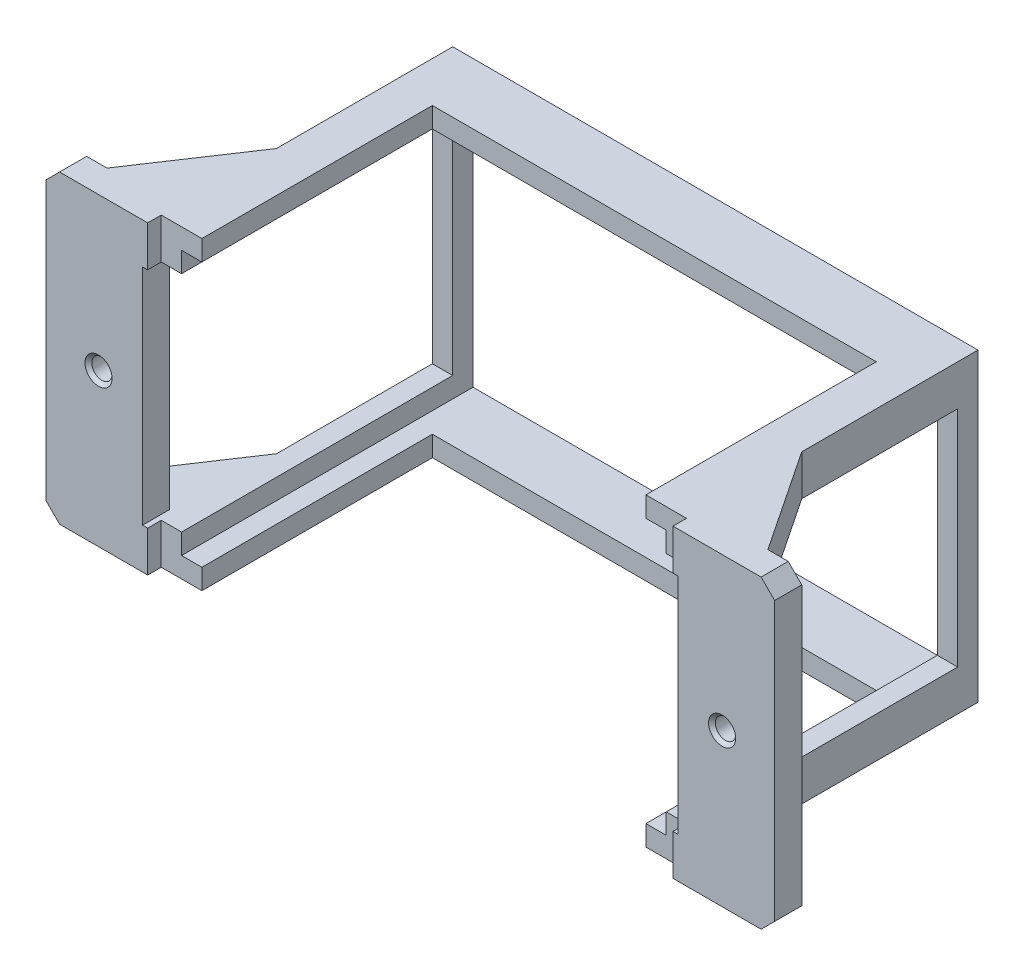
SolidWorks part; units mm, degrees
ref_plane "前视基准面" through (0, 0, 0) normal (0, 0, 1) x (1, 0, 0)
ref_plane "上视基准面" through (0, 0, 0) normal (0, 1, 0) x (1, 0, 0)
ref_plane "右视基准面" through (0, 0, 0) normal (1, 0, 0) x (0, 0, -1)
sketch "草图1" plane through (0, 0, 0) normal (0, 0, 1) x (1, 0, 0)
  line L0 (-38.75, 22.5) -> (38.75, 22.5)
  line L1 (-35.75, 19.5) -> (35.75, 19.5)
  line L2 (-35.75, 19.5) -> (-35.75, -19.5)
  line L3 (-35.75, -19.5) -> (35.75, -19.5)
  line L4 (35.75, 19.5) -> (35.75, -19.5)
  line L5 (38.75, 22.5) -> (38.75, -22.5)
  line L6 (-38.75, -22.5) -> (38.75, -22.5)
  line L7 (-38.75, 22.5) -> (-38.75, -22.5)
  dimension "D1" = 71.5
  dimension "D2" = 35.75
  dimension "D3" = 39
  dimension "D4" = 19.5
  dimension "D5" = 3
extrude "凸台-拉伸1" add sketch "草图1" along normal blind 3
sketch "草图2" plane through (0, 0, 3) normal (0, 0, 1) x (1, 0, 0)
  line L0 (0, 0) -> (0, 50000) construction
  line L1 (38.75, 22.5) -> (35.75, 22.5)
  line L2 (38.75, 22.5) -> (38.75, 19.5)
  line L3 (38.75, 19.5) -> (35.75, 19.5)
  line L4 (35.75, 22.5) -> (35.75, 19.5)
  line L5 (0, 0) -> (50000, 0) construction
  line L6 (-35.75, 22.5) -> (-35.75, 19.5)
  line L7 (-38.75, 19.5) -> (-35.75, 19.5)
  line L8 (-38.75, 22.5) -> (-38.75, 19.5)
  line L9 (-38.75, 22.5) -> (-35.75, 22.5)
  line L10 (-38.75, -22.5) -> (-35.75, -22.5)
  line L11 (-38.75, -22.5) -> (-38.75, -19.5)
  line L12 (-38.75, -19.5) -> (-35.75, -19.5)
  line L13 (-35.75, -22.5) -> (-35.75, -19.5)
  line L14 (35.75, -22.5) -> (35.75, -19.5)
  line L15 (38.75, -19.5) -> (35.75, -19.5)
  line L16 (38.75, -22.5) -> (38.75, -19.5)
  line L17 (38.75, -22.5) -> (35.75, -22.5)
extrude "凸台-拉伸2" add sketch "草图2" along normal blind 40
sketch "草图3" plane through (0, 0, 3) normal (0, 0, 1) x (1, 0, 0)
  line L0 (38.75, -19.5) -> (38.75, 19.5) construction
  line L1 (35.75, 19.5) -> (38.75, 19.5)
  line L2 (35.75, 19.5) -> (35.75, 16.5)
  line L3 (35.75, 16.5) -> (38.75, 16.5)
  line L4 (38.75, 19.5) -> (38.75, 16.5)
  line L5 (35.75, 22.5) -> (-35.75, 22.5) construction
  line L6 (35.75, 19.5) -> (32.75, 19.5)
  line L7 (35.75, 19.5) -> (35.75, 22.5)
  line L8 (35.75, 22.5) -> (32.75, 22.5)
  line L9 (32.75, 19.5) -> (32.75, 22.5)
  line L10 (0, 0) -> (0, 50000) construction
  line L11 (0, 0) -> (50000, 0) construction
  line L12 (-32.75, 19.5) -> (-32.75, 22.5)
  line L13 (-35.75, 22.5) -> (-32.75, 22.5)
  line L14 (-35.75, 19.5) -> (-35.75, 22.5)
  line L15 (-35.75, 19.5) -> (-32.75, 19.5)
  line L16 (-38.75, 19.5) -> (-38.75, 16.5)
  line L17 (-35.75, 16.5) -> (-38.75, 16.5)
  line L18 (-35.75, 19.5) -> (-35.75, 16.5)
  line L19 (-35.75, 19.5) -> (-38.75, 19.5)
  line L20 (-35.75, -19.5) -> (-38.75, -19.5)
  line L21 (-35.75, -19.5) -> (-35.75, -16.5)
  line L22 (-35.75, -16.5) -> (-38.75, -16.5)
  line L23 (-38.75, -19.5) -> (-38.75, -16.5)
  line L24 (-35.75, -19.5) -> (-32.75, -19.5)
  line L25 (-35.75, -19.5) -> (-35.75, -22.5)
  line L26 (-35.75, -22.5) -> (-32.75, -22.5)
  line L27 (-32.75, -19.5) -> (-32.75, -22.5)
  line L28 (32.75, -19.5) -> (32.75, -22.5)
  line L29 (35.75, -22.5) -> (32.75, -22.5)
  line L30 (35.75, -19.5) -> (35.75, -22.5)
  line L31 (35.75, -19.5) -> (32.75, -19.5)
  line L32 (38.75, -19.5) -> (38.75, -16.5)
  line L33 (35.75, -16.5) -> (38.75, -16.5)
  line L34 (35.75, -19.5) -> (35.75, -16.5)
  line L35 (35.75, -19.5) -> (38.75, -19.5)
  line M5 (35.75, 19.5) -> (35.75, -19.5)
  line M6 (35.75, -19.5) -> (38.75, -19.5)
  line M7 (38.75, -19.5) -> (38.75, 19.5)
  line M8 (38.75, 19.5) -> (35.75, 19.5)
  dimension "D1" = 3
  dimension "D2" = 3
extrude "凸台-拉伸3" add sketch "草图3" along normal blind 40 contours L23 L20 L21 L22 | L27 L24 L25 L26 | L30 L31 L28 L29 | L33 M5 M6 M7 | L3 M5 M7 M8 | L9 L6 L7 L8 | L14 L15 L12 L13 | L18 L19 L16 L17 region at (34.25, -21, 3) region at (37.25, 18, 3) region at (34.25, 21, 3) region at (37.25, -18, 3) region at (-34.25, 21, 3) region at (-37.25, 18, 3) region at (-37.25, -18, 3) region at (-34.25, -21, 3)
sketch "草图4" plane through (0, 0, 43) normal (0, 0, 1) x (1, 0, 0)
  line L0 (38.75, -22.5) -> (38.75, -16.5) construction
  line L1 (38.75, 22.5) -> (53.75, 22.5)
  line L2 (38.75, 22.5) -> (38.75, 16.5)
  line L3 (38.75, 16.5) -> (39.5, 16.5)
  line L6 (39.5, 16.5) -> (39.5, -16.5)
  line L9 (39.5, -16.5) -> (38.75, -16.5)
  line L10 (53.75, 22.5) -> (53.75, -22.5)
  line L11 (53.75, -22.5) -> (38.75, -22.5)
  line L12 (38.75, -16.5) -> (38.75, -22.5)
  line L13 (32.75, -22.5) -> (38.75, -22.5) construction
  line L14 (35.75, -16.5) -> (38.75, -16.5) construction
  line L15 (35.75, 16.5) -> (38.75, 16.5) construction
  line L16 (0, 0) -> (0, 50000) construction
  line L17 (-38.75, -16.5) -> (-38.75, -22.5)
  line L18 (-53.75, -22.5) -> (-38.75, -22.5)
  line L19 (-53.75, 22.5) -> (-53.75, -22.5)
  line L20 (-39.5, -16.5) -> (-38.75, -16.5)
  line L21 (-39.5, 16.5) -> (-39.5, -16.5)
  line L22 (-38.75, 16.5) -> (-39.5, 16.5)
  line L23 (-38.75, 22.5) -> (-38.75, 16.5)
  line L24 (-38.75, 22.5) -> (-53.75, 22.5)
  dimension "D1" = 39.5
  dimension "D2" = 15
extrude "凸台-拉伸4" add sketch "草图4" along normal blind 2 and the other way blind 2 separate body
sketch "草图5" plane through (0, 22.5, 0) normal (0, 1, 0) x (1, 0, 0)
  line L0 (32.75, -43) -> (32.75, -3) construction
  line L1 (32.75, -9) -> (-32.75, -9)
  line L2 (32.75, -9) -> (32.75, -3)
  line L3 (32.75, -3) -> (-32.75, -3)
  line L4 (-32.75, -9) -> (-32.75, -3)
  dimension "D1" = 6
extrude "凸台-拉伸5" add sketch "草图5" against normal blind 3
sketch "草图6" plane through (0, -22.5, 0) normal (0, -1, 0) x (1, 0, 0)
  line L4 (32.75, 9) -> (-32.75, 9)
  line L5 (-32.75, 9) -> (-32.75, 3)
  line L6 (-32.75, 3) -> (32.75, 3)
  line L7 (32.75, 3) -> (32.75, 9)
  line L8 (32.75, 9) -> (-32.75, 9)
  line L9 (-32.75, 9) -> (-32.75, 3)
  line L10 (-32.75, 3) -> (32.75, 3)
  line L11 (32.75, 3) -> (32.75, 9)
  dimension "D1" = 0
extrude "凸台-拉伸6" add sketch "草图6" against normal blind 3 separate body
sketch "草图7" plane through (0, 0, 45) normal (0, 0, 1) x (1, 0, 0)
  line L0 (0, 0) -> (0, 50000) construction
  circle A0 centre (-46, 0) radius 1.5
  circle A1 centre (46, 0) radius 1.5
  dimension "D1" = 46
  dimension "D2" = 3
extrude "切除-拉伸1" cut sketch "草图7" against normal blind 5
chamfer "倒角1" distance 0.5 angle 45 1 edges at (-44.5, 0, 45)
chamfer "倒角2" distance 0.5 angle 45 1 edges at (44.5, 0, 45)
chamfer "倒角3" distance 2 angle 45 2 edges at (53.75, -22.5, 43) (53.75, 22.5, 43)
combine bodies "组合1" operation type add bodies to combine 112 117
combine bodies "组合2" operation type add bodies to combine 113 118
combine bodies "组合3" operation type add bodies to combine 116 119
chamfer "倒角4" distance 2 angle 45 2 edges at (-53.75, -22.5, 43) (-53.75, 22.5, 43)
sketch "草图8" plane through (0, 22.5, 0) normal (0, 1, 0) x (1, 0, 0)
  line L0 (48.75, -41) -> (38.75, -26)
  line L1 (51.75, -41) -> (38.75, -41) construction
  line L2 (38.75, -41) -> (38.75, 0) construction
  line L3 (38.75, -26) -> (38.75, -41)
  line L4 (38.75, -41) -> (48.75, -41)
  line L5 (0, 0.5284) -> (0, 50000.5284) construction
  dimension "D1" = 10
  dimension "D2" = 15
extrude "凸台-拉伸7" add sketch "草图8" against normal blind 6
mirror "镜向1" about plane through (0, 0, 0) normal (1, 0, 0) of "凸台-拉伸7"
mirror "镜向2" about plane through (0, 0, 0) normal (0, 1, 0) of "镜向1"
